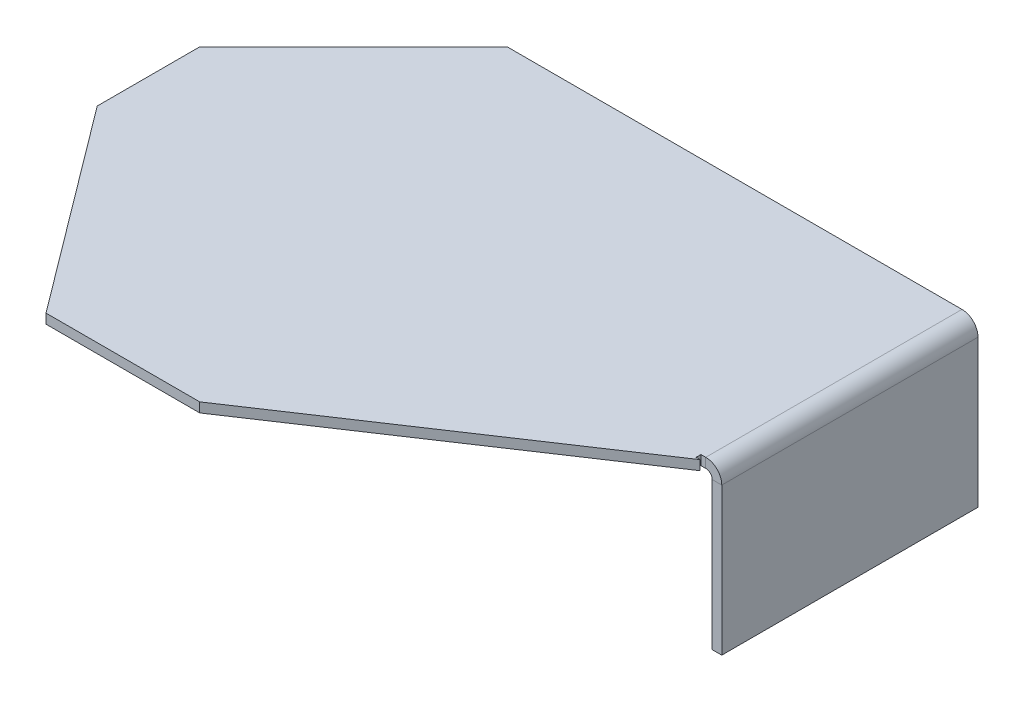
SolidWorks part; units mm, degrees
note: The reader was unsure of these and kept them because the rebuilt part matched: thickness of "Base-Flange1", "Edge-Flange1", "Sheet-Metal4", "Sheet-Metal5"; flange length of "Edge-Flange1".
material "ASTM A36 Steel"
ref_plane "Front Plane" through (0, 0, 0) normal (0, 0, 1) x (1, 0, 0)
ref_plane "Top Plane" through (0, 0, 0) normal (0, 1, 0) x (1, 0, 0)
ref_plane "Right Plane" through (0, 0, 0) normal (1, 0, 0) x (0, 0, -1)
sketch "Sketch1" plane through (0, 0, 0) normal (0, 1, 0) x (1, 0, 0)
  line L0 (304.8, 50.8) -> (304.8, 203.2)
  line L1 (-304.8, -50.8) -> (304.8, -50.8) construction
  line L2 (-304.8, -50.8) -> (-304.8, 50.8)
  line L3 (-304.8, 50.8) -> (304.8, 50.8) construction
  line L4 (304.8, -50.8) -> (304.8, 50.8)
  line L5 (-304.8, -50.8) -> (304.8, 50.8) construction
  line L6 (-304.8, 50.8) -> (304.8, -50.8) construction
  line L7 (304.8, 203.2) -> (-152.4, 203.2)
  line L8 (-152.4, 203.2) -> (-304.8, 50.8)
  line L9 (-304.8, -50.8) -> (-152.4, -254)
  line L10 (-152.4, -254) -> (0, -254)
  line L11 (0, -254) -> (304.8, -50.8)
  point P0 (0, 0)
  dimension "D1" = 609.6
  dimension "D2" = 101.6
  dimension "D3" = 152.4
  dimension "D4" = 45
  dimension "D5" = 152.4
  dimension "D7" = 203.2
base flange "Base-Flange1" sketch "Sketch1" thickness 9.525 reverse thickness direction no parameters "D1"=6.3754
edge flange "Edge-Flange1" sketch "Sketch8" flange angle 90 flange length 152.4 flange position material outside bend radius 6.3754 thickness 9.525 relief rectangular parameters "D6"=10
sketch "Sketch8" plane through (304.8, -9.525, 0) normal (1, 0, 0) x (0, 0, 1)
  line L2 (-203.2, 0) -> (-203.2, 152.4)
  line L3 (-203.2, 152.4) -> (50.8, 152.4)
  line L4 (50.8, 152.4) -> (50.8, 0)
  line L7 (50.8, 0) -> (-203.2, 0) construction
  line L8 (50.8, 0) -> (-203.2, 0)
bend "EdgeBend1" bend radius 6.3754 bend angle 90 parameters "D5"=1
sketch "Bend-Lines1" [suppressed] plane through (0, 0, 0) normal (0, 1, 0) x (1, 0, 0)
sketch "Bounding-Box1" [suppressed] plane through (0, 0, 0) normal (0, 1, 0) x (1, 0, 0)
sheet metal parameters "Sheet-Metal4" thickness 9.525 parameters "D1"=6.3754, "D7"=6.35
flat pattern "Flat-Pattern4" [suppressed]
sketch "Bend-Lines2" plane through (0, 0, 0) normal (0, 1, 0) x (1, 0, 0)
sketch3d "Bounding-Box2" [suppressed]
  line L0 (304.8, -254, 0) -> (-304.8, -254, 0) construction
  line L1 (304.8, 203.2, 0) -> (-304.8, 203.2, 0) construction
  line L2 (304.8, -254, 0) -> (304.8, 203.2, 0) construction
  line L3 (-304.8, -254, 0) -> (-304.8, 203.2, 0) construction
sheet metal parameters "Sheet-Metal5" thickness 9.525 parameters "D1"=6.3754, "D7"=6.35
flat pattern "Flat-Pattern4"
sketch "Bend-Lines2" plane through (0, 0, 0) normal (0, 1, 0) x (1, 0, 0)
  line L0 (307.1723, -50.8) -> (307.1723, 203.2) construction
  line L1 (307.1723, -50.8) -> (307.1723, 203.2) construction
sketch3d "Bounding-Box2" [suppressed]
  line L0 (461.9446, -254, 0) -> (-304.8, -254, 0) construction
  line L1 (461.9446, 203.2, 0) -> (-304.8, 203.2, 0) construction
  line L2 (461.9446, -254, 0) -> (461.9446, 203.2, 0) construction
  line L3 (-304.8, -254, 0) -> (-304.8, 203.2, 0) construction
bend of the flat pattern "Flatten-<EdgeBend1>1"
equation "\"PRIMER_USAGE\"= ( \"SW-SurfaceArea\" / 144 ) / 135"
equation "\"WET_PAINT_USAGE\"= ( \"SW-SurfaceArea\" / 144 ) / 125"
equation "\"POWDERCOAT_USAGE\"= ( \"SW-SurfaceArea\" / 144 ) / 29.79"
equation "\"DECKOVER_USAGE\"= ( \"SW-SurfaceArea\" / 144 ) / 75"
equation "\"SW_NON-SKID\"= ( \"SW-SurfaceArea\" / 144 ) / 165"
equation "\"TYPE_1_ANODIZATING\"= ( \"SW-SurfaceArea\" * 0.0001 )"
equation "\"TYPE_2_ANODIZING\"= ( \"SW-SurfaceArea\" * 0.0005 )"
equation "\"TYPE_3_ANODIZING-HARDCOAT\"= ( \"SW-SurfaceArea\" * 0.003 )"
